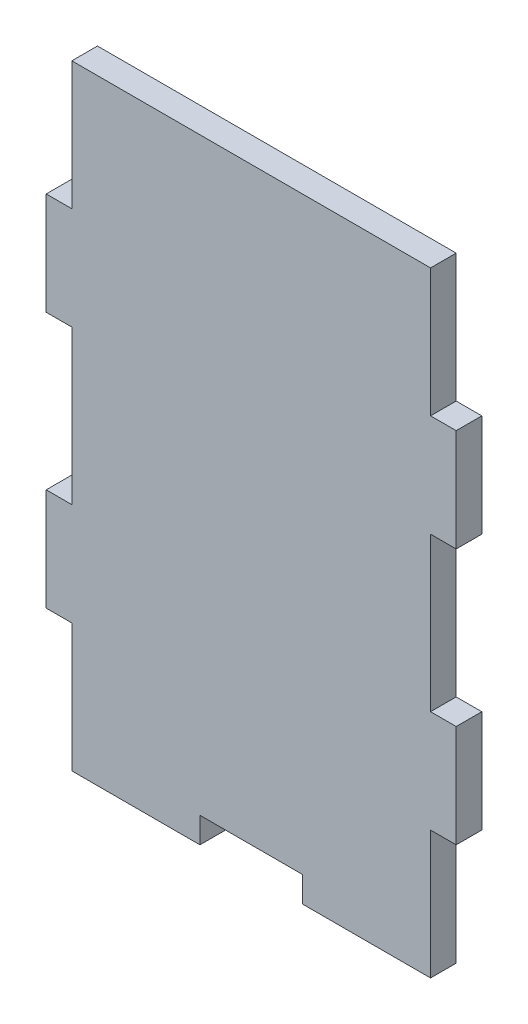
SolidWorks part; units mm, degrees
ref_plane "Front Plane" through (0, 0, 0) normal (0, 0, 1) x (1, 0, 0)
ref_plane "Top Plane" through (0, 0, 0) normal (0, 1, 0) x (1, 0, 0)
ref_plane "Right Plane" through (0, 0, 0) normal (1, 0, 0) x (0, 0, -1)
sketch "Sketch1" plane through (0, 0, 0) normal (0, 0, 1) x (1, 0, 0)
  line L0 (-64.6057, 122.8342) -> (-64.6057, -48.6158) construction
  line L1 (-109.0557, 122.8342) -> (-20.1557, 122.8342)
  line L2 (-109.0557, 122.8342) -> (-109.0557, -29.5658)
  line L3 (-109.0557, -29.5658) -> (-77.3057, -29.5658)
  line L4 (-20.1557, 122.8342) -> (-20.1557, -29.5658)
  line L5 (-109.0557, 46.6342) -> (-20.1557, 46.6342) construction
  line L6 (-13.8057, 2.1842) -> (-20.1557, 2.1842)
  line L7 (-115.4057, 27.5842) -> (-109.0557, 27.5842)
  line L8 (-115.4057, 27.5842) -> (-115.4057, 2.1842)
  line L9 (-115.4057, 2.1842) -> (-109.0557, 2.1842)
  line L10 (-51.9057, -29.5658) -> (-44.9709, -29.5658) construction
  line L11 (-51.9057, -29.5658) -> (-44.9709, -29.5658)
  line L12 (-115.4057, 91.0842) -> (-109.0557, 91.0842)
  line L13 (-77.3057, -29.5658) -> (-51.9057, -29.5658)
  line L14 (-77.3057, -29.5658) -> (-77.3057, -23.2158)
  line L15 (-13.8057, 27.5842) -> (-13.8057, 2.1842)
  line L16 (-13.8057, 27.5842) -> (-20.1557, 27.5842)
  line L17 (-77.3057, -23.2158) -> (-51.9057, -23.2158)
  line L18 (-51.9057, -29.5658) -> (-51.9057, -23.2158)
  line L19 (-115.4057, 65.6842) -> (-115.4057, 91.0842)
  line L20 (-115.4057, 65.6842) -> (-109.0557, 65.6842)
  line L21 (-13.8057, 65.6842) -> (-20.1557, 65.6842)
  line L22 (-13.8057, 65.6842) -> (-13.8057, 91.0842)
  line L23 (-13.8057, 91.0842) -> (-20.1557, 91.0842)
  line L27 (-20.1557, -29.5658) -> (-51.9057, -29.5658)
  dimension "D2" = 88.9
  dimension "D3" = 6.35
  dimension "D4" = 25.4
  dimension "D5" = 31.75
  dimension "D6" = 25.4
  dimension "D7" = 6.35
extrude "Boss-Extrude1" add sketch "Sketch1" along normal blind 6.35 contours L27 L4 L1 L2 L3 L14 L17 L18 L11 | L19 L20 L2 L12 | L8 L9 L2 L7 | L15 L16 L4 L6 | L22 L23 L4 L21 region at (-64.6057, 47.5141, 0) region at (-112.2307, 78.3842, 0) region at (-16.9807, 78.3842, 0) region at (-112.2307, 14.8842, 0) region at (-16.9807, 14.8842, 0)
equation "\"width\"= 3.5in"
equation "\"Height\"= 18in"
equation "\"thick\"= 0.25"
equation "\"D3@Sketch1\"=\"thick\""
equation "\"D2@Sketch1\"=\"width\""
equation "\"D7@Sketch1\"=\"thick\""
equation "\"D1@Boss-Extrude1\"=\"thick\""
